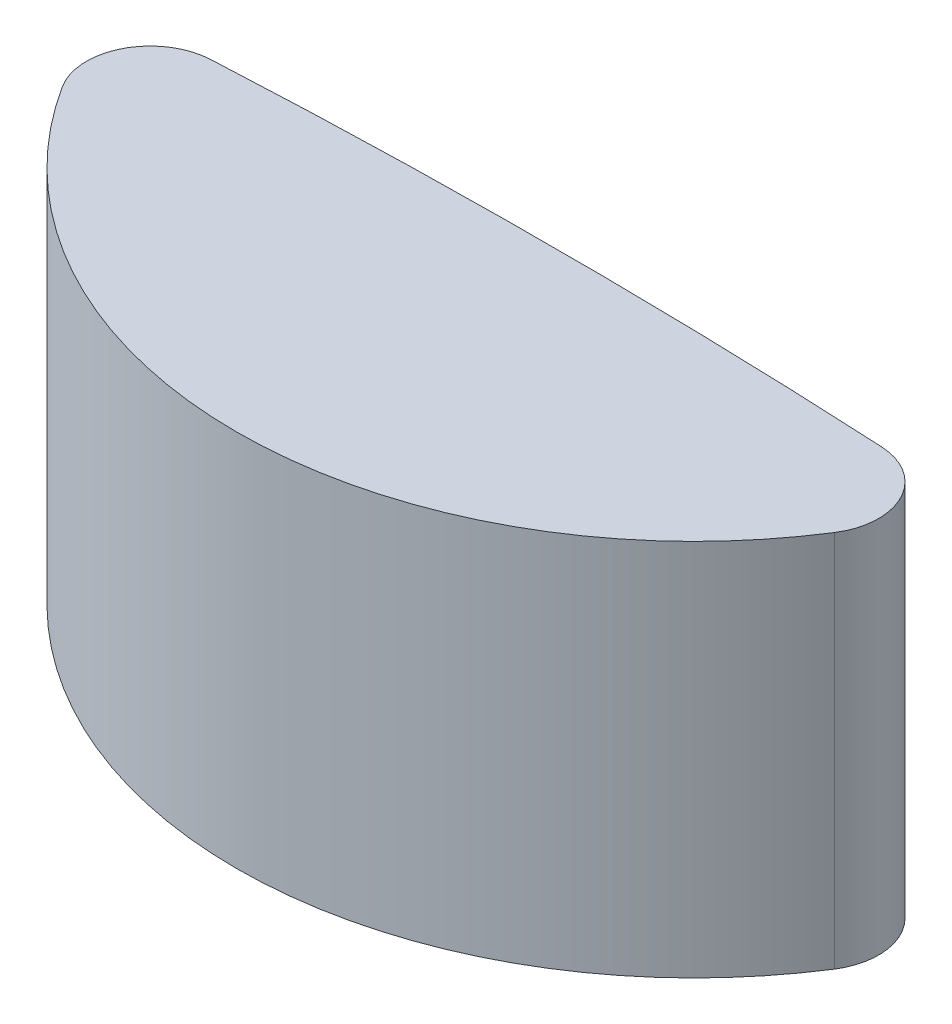
SolidWorks part; units mm, degrees
ref_plane "Front Plane" through (0, 0, 0) normal (0, 0, 1) x (1, 0, 0)
ref_plane "Top Plane" through (0, 0, 0) normal (0, 1, 0) x (1, 0, 0)
ref_plane "Right Plane" through (0, 0, 0) normal (1, 0, 0) x (0, 0, -1)
sketch "Sketch2" plane through (0, 0, 0) normal (0, 1, 0) x (1, 0, 0)
  line L0 (0, 109.5161) -> (0, 105.4521) construction
  arc A0 (-4.2854, 109.4041) -> (-4.9281, 108.1568) centre (-4.243, 108.593) ccw
  arc A1 (4.2854, 109.4041) -> (-4.2854, 109.4041) centre (0, 27.4741) ccw
  arc A2 (-4.9281, 108.1568) -> (4.9281, 108.1568) centre (0, 111.2941) ccw
  arc A3 (4.2854, 109.4041) -> (4.9281, 108.1568) centre (4.243, 108.593) cw
  point P6 (0, 109.5161)
  point P9 (0, 105.4521)
  dimension "D1" = 164.084
  dimension "D4" = 11.684
  dimension "D3" = 4.064
extrude "Boss-Extrude2" add sketch "Sketch2" along normal blind 4.826
